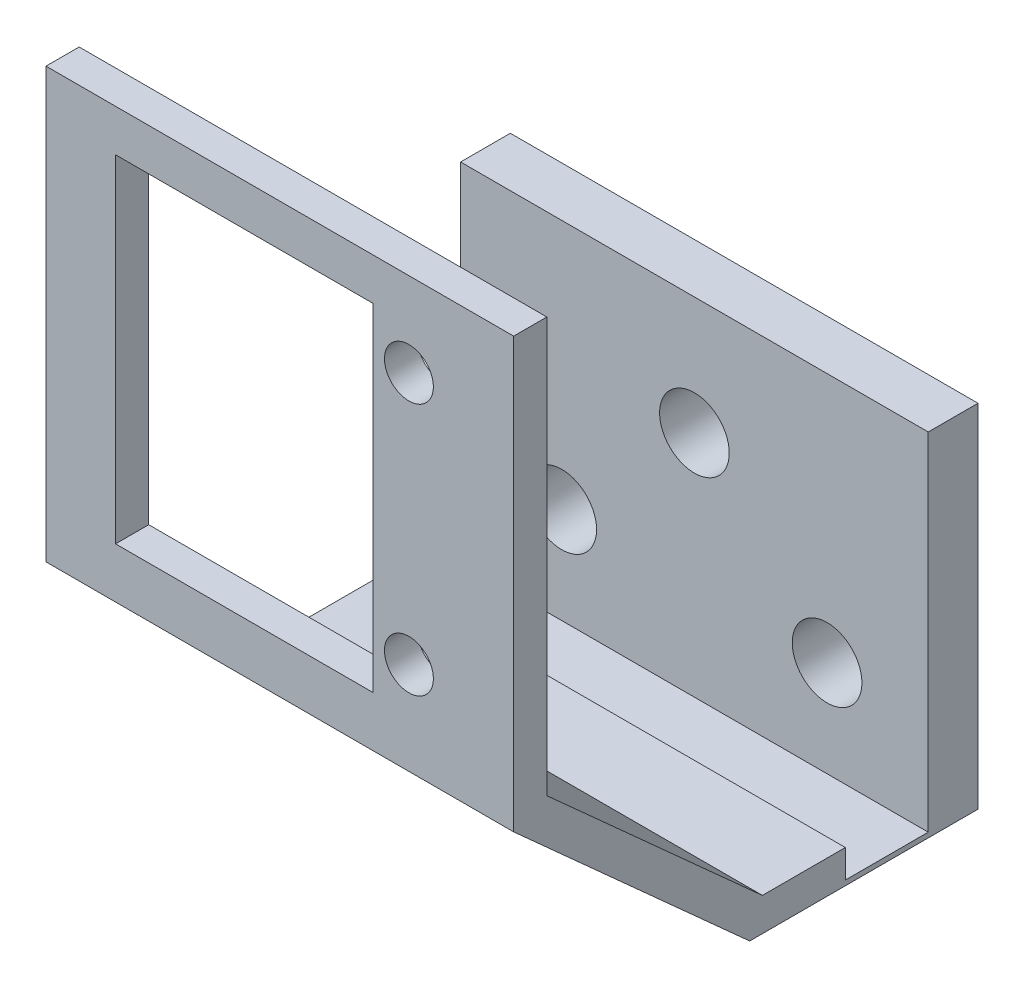
SolidWorks part; units mm, degrees
ref_plane "Front Plane" through (0, 0, 0) normal (0, 0, 1) x (1, 0, 0)
ref_plane "Top Plane" through (0, 0, 0) normal (0, 1, 0) x (1, 0, 0)
ref_plane "Right Plane" through (0, 0, 0) normal (1, 0, 0) x (0, 0, -1)
sketch "Sketch2" plane through (0, 0, 0) normal (0, 0, 1) x (1, 0, 0)
  line L1 (-76.6, -15) -> (-48.4, -15)
  line L2 (-76.6, -15) -> (-76.6, 6.2)
  line L3 (-76.6, 6.2) -> (-48.4, 6.2)
  line L4 (-48.4, -15) -> (-48.4, 6.2)
  line L5 (-50.4, -15) -> (-74.6, -15) construction
  line L6 (-48.4, -2) -> (-48.4, -13) construction
  line L7 (-74.6, 6.2) -> (-50.4, 6.2) construction
  circle A0 centre (-54.5, -8.9) radius 2.1
  circle A1 centre (-70.5, -8.9) radius 2.1
  circle A2 centre (-62.5, -0.9) radius 2.1
  circle A3 centre (-54.5, -8.9) radius 2.1 construction
  circle A4 centre (-70.5, -8.9) radius 2.1 construction
  circle A5 centre (-62.5, -0.9) radius 2.1 construction
  point P7 (-62.5, -15)
  point P8 (-62.5, -15)
extrude "Boss-Extrude1" add sketch "Sketch2" along normal blind 3
sketch "Sketch3" plane through (0, 0, 3) normal (0, 0, 1) x (1, 0, 0)
  line L0 (-76.6, 6.2) -> (-76.6, -15) construction
  line L1 (-48.4, -15) -> (-76.6, -15)
  line L2 (-48.4, -15) -> (-48.4, -14.7)
  line L3 (-48.4, -14.7) -> (-76.6, -14.7)
  line L4 (-76.6, -15) -> (-76.6, -14.7)
  dimension "D1" = 0.3
extrude "Boss-Extrude2" add sketch "Sketch3" along normal blind 5
sketch "Sketch6" plane through (-76.6, 0, 0) normal (-1, 0, 0) x (0, 0, 1)
  line L0 (8, -15) -> (13.7677, -15)
  line L1 (13.7677, -15) -> (28, -2.1852)
  line L2 (28, -2.1852) -> (28, 23.7053)
  line L3 (28, 23.7053) -> (26, 23.7053)
  line L4 (26, 23.7053) -> (26, -1.2947)
  line L5 (26, -1.2947) -> (13, -13)
  line L6 (13, -13) -> (8, -13)
  line L7 (8, -13) -> (8, -15)
  line L8 (3, 6.2) -> (3, -14.7) construction
  dimension "D1" = 2
  dimension "D2" = 2
  dimension "D3" = 2
  dimension "D4" = 42
  dimension "D5" = 25
  dimension "D6" = 5
  dimension "D7" = 23
extrude "Boss-Extrude5" add sketch "Sketch6" against normal up to surface (28.2 mm away) up to face at (-48.4, -7.8333, 3.6667)
sketch "Sketch7" plane through (0, 0, 28) normal (0, 0, 1) x (1, 0, 0)
  line L1 (-72.406, 21.174) -> (-56.886, 21.174)
  line L2 (-72.406, 21.174) -> (-72.406, 0.854)
  line L3 (-72.406, 0.854) -> (-56.886, 0.854)
  line L4 (-52.086, 21.174) -> (-52.086, 0.854) construction
  line L5 (-48.4, 23.7053) -> (-76.6, 23.7053) construction
  line L6 (-56.886, 0.854) -> (-56.886, 21.174)
  line L7 (-56.886, 21.174) -> (-52.086, 21.174) construction
  line L8 (-56.886, 0.854) -> (-52.086, 0.854) construction
  line L9 (-48.4, 23.7053) -> (-48.4, -2.1852) construction
  line L10 (-54.716, 18.634) -> (-54.716, 3.394) construction
  circle A0 centre (-54.716, 3.394) radius 1.475
  circle A1 centre (-54.716, 18.634) radius 1.475
  point P0 (-62.5, 10.76)
  point P8 (-62.5, 23.7053)
  point P12 (-54.716, 11.014)
  point P13 (-52.086, 11.014)
  point P18 (-48.4, 10.76)
  dimension "D7" = 2.95
  dimension "D1" = 10.414
  dimension "D2" = 9.906
  dimension "D3" = 20.32
  dimension "D4" = 20.32
  dimension "D5" = 4.8
  dimension "D6" = 15.24
  dimension "D8" = 2.63
extrude "Cut-Extrude1" cut sketch "Sketch7" against normal up to next
equation "\"D2@Sketch6\"=\"D1@Sketch6\""
equation "\"D3@Sketch6\"=\"D2@Sketch6\""
equation "\"width\"= 24"
equation "\"thk\"= 3"
equation "\"holesize\"= 4.2"
equation "\"holedistance\"= ( 20 + 12 ) / 2"
equation "\"threaded_hole\"= 3.9"
equation "\"fillet_radius\"= 2"
equation "\"ground_clearance\"= 25"
equation "\"tire_thk\"= 3"
equation "\"innerwheel_diam\" = \"wheel_diam\"-2*\"tire_thk\""
equation "\"innerwheel_thk\"= 8"
equation "\"wheel_diam\"= 2*(\"width\"/2+\"ground_clearance\")"
equation "\"coloursensor_holesize\"= 2.65"
equation "\"hole_to_edge\" = 4"
equation "\"D7@Sketch7\"=\"coloursensor_holesize\"+0.3"
